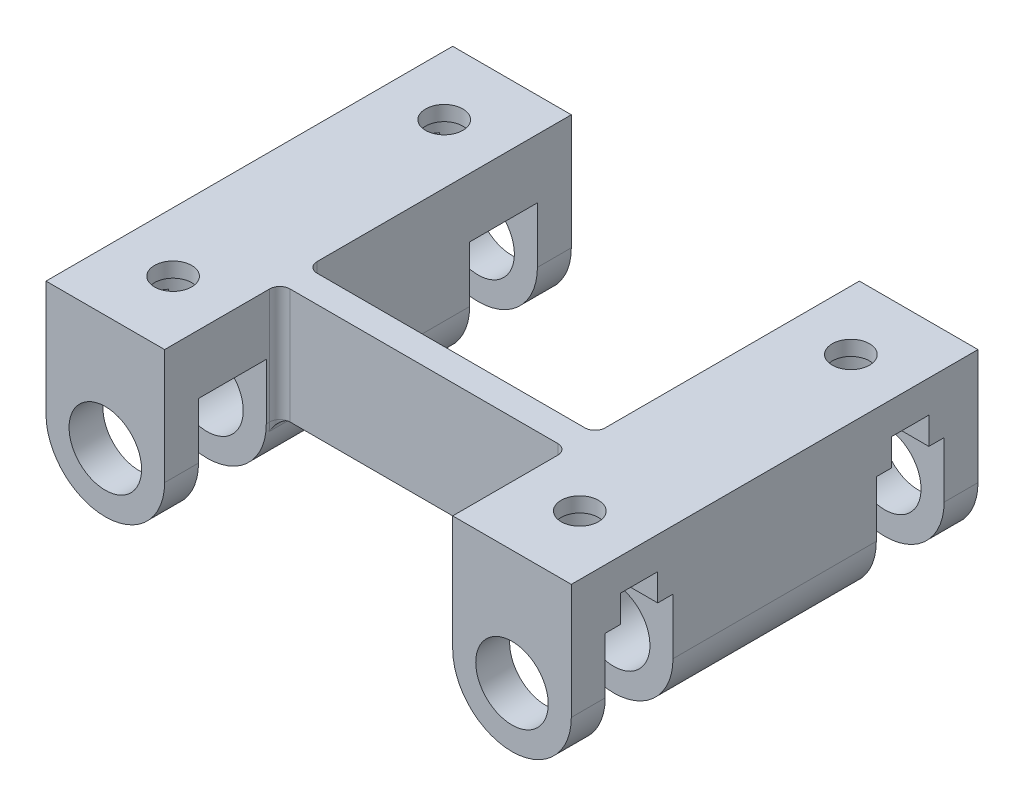
SolidWorks part; units mm, degrees
ref_plane "Front Plane" through (0, 0, 0) normal (0, 0, 1) x (1, 0, 0)
ref_plane "Top Plane" through (0, 0, 0) normal (0, 1, 0) x (1, 0, 0)
ref_plane "Right Plane" through (0, 0, 0) normal (1, 0, 0) x (0, 0, -1)
sketch "Sketch1" plane through (0, 0, 0) normal (0, 0, 1) x (1, 0, 0)
  line L1 (-8.75, 0) -> (8.75, 0)
  line L2 (-8.75, 0) -> (-8.75, 17)
  line L3 (-8.75, 17) -> (8.75, 17)
  line L4 (8.75, 0) -> (8.75, 17)
  circle A0 centre (0, 0) radius 5.35
  circle A1 centre (0, 0) radius 8.75
  dimension "D1" = 10.7
  dimension "D2" = 17.5
  dimension "D3" = 17
  dimension "D4" = 17.5
extrude "Boss-Extrude2" add sketch "Sketch1" along normal mid plane 60 contours L1 A1 A0 | L1 A1 A0 | A1 L4 L3 L2 region at (0, 5.5457, 0) region at (7.05, -0.1957, 0) region at (0, 11.7478, 0)
sketch "Sketch5" plane through (-8.75, 0, 0) normal (-1, 0, 0) x (0, 0, 1)
  line L0 (-30, -8.75) -> (30, -8.75) construction
  line L1 (-25, 8.25) -> (-15, 8.25)
  line L2 (-25, 8.25) -> (-25, -8.75)
  line L3 (-25, -8.75) -> (-15, -8.75)
  line L4 (-15, 8.25) -> (-15, -8.75)
  line L5 (-30, 0) -> (-30, 17) construction
  line L6 (30, 0) -> (30, 17) construction
  line L7 (15, 8.25) -> (25, 8.25)
  line L8 (15, 8.25) -> (15, -8.75)
  line L9 (15, -8.75) -> (25, -8.75)
  line L10 (25, 8.25) -> (25, -8.75)
  dimension "D1" = 5
  dimension "D2" = 10
  dimension "D3" = 17
  dimension "D4" = 5
  dimension "D5" = 10
  dimension "D6" = 17
extrude "Cut-Extrude5" cut sketch "Sketch5" against normal blind 18 contours L2 L1 L4 L3 | L8 L7 L10 L9
sketch "Sketch7" plane through (0, 8.25, 0) normal (0, -1, 0) x (1, 0, 0)
  line L0 (8.75, 15) -> (8.75, 25) construction
  circle A0 centre (0, 20) radius 4.4
  point P7 (8.75, 20)
  dimension "D1" = 8.8
extrude "Cut-Extrude7" cut sketch "Sketch7" against normal blind 6.55
sketch "Sketch8" plane through (0, 14.8, 0) normal (0, -1, 0) x (1, 0, 0)
  line L0 (8.75, 15) -> (8.75, 25) construction
  circle A0 centre (0, 20) radius 2.75
  point P6 (8.75, 20)
  dimension "D1" = 5.5
extrude "Cut-Extrude8" cut sketch "Sketch8" against normal blind 2.2 contours A0
sketch "Sketch9" plane through (0, 8.25, 0) normal (0, -1, 0) x (1, 0, 0)
  line L0 (-8.75, 15) -> (-8.75, 25) construction
  line L1 (0, 17.25) -> (-8.75, 17.25)
  line L2 (0, 17.25) -> (0, 22.75)
  line L3 (0, 22.75) -> (-8.75, 22.75)
  line L4 (-8.75, 17.25) -> (-8.75, 22.75)
  circle A0 centre (0, 20) radius 2.75 construction
  dimension "D1" = 5.5
  dimension "D2" = 8.75
extrude "Cut-Extrude11" cut sketch "Sketch9" against normal blind 4 contours L2 L1 L4 L3
sketch "Sketch10" plane through (0, 8.25, 0) normal (0, -1, 0) x (1, 0, 0)
  line L0 (8.75, -25) -> (8.75, -15) construction
  circle A0 centre (0, -20) radius 4.4
  point P8 (8.75, -20)
extrude "Cut-Extrude12" cut sketch "Sketch10" against normal blind 6.55 contours A0
sketch "Sketch11" plane through (0, 14.8, 0) normal (0, -1, 0) x (-1, 0, 0)
  circle A0 centre (0, 20) radius 2.75
  dimension "D1" = 5.5
extrude "Cut-Extrude13" cut sketch "Sketch11" against normal blind 2.2 contours A0
sketch "Sketch13" plane through (0, 14.8, 0) normal (0, -1, 0) x (1, 0, 0)
  line L0 (-8.75, -25) -> (-8.75, -15) construction
  line L1 (0, -22.75) -> (-8.75, -22.75)
  line L2 (0, -22.75) -> (0, -17.25)
  line L3 (0, -17.25) -> (-8.75, -17.25)
  line L4 (-8.75, -22.75) -> (-8.75, -17.25)
  circle A0 centre (0, -20) radius 2.75 construction
  dimension "D1" = 5.5
  dimension "D2" = 8.75
extrude "Cut-Extrude14" cut sketch "Sketch13" against normal blind 4 from offset 6.55 contours L2 L1 L4 L3
ref_plane "Plane1" through (30, 0, 0) normal (1, 0, 0) x (0, 0, -1)
sketch "Sketch14" plane through (8.75, 0, 0) normal (1, 0, 0) x (0, 0, -1)
  line L0 (-30, 17) -> (30, 17) construction
  line L1 (-13, 17) -> (-9, 17)
  line L2 (-13, 17) -> (-13, 0)
  line L3 (-13, 0) -> (-9, 0)
  line L4 (-9, 17) -> (-9, 0)
  line L5 (-15, 0) -> (15, 0) construction
  line L6 (-30, 0) -> (-30, 17) construction
  dimension "D1" = 4
  dimension "D2" = 17
extrude "Boss-Extrude4" add sketch "Sketch14" along normal up to surface (21.25 mm away) up to plane "Plane1"
mirror "Mirror4" about plane through (30, 0, 0) normal (1, 0, 0) of "Boss-Extrude4"
mirror "Mirror5" about plane through (30, 0, 0) normal (1, 0, 0) of "Boss-Extrude2"
mirror "Mirror6" about plane through (30, 0, 0) normal (1, 0, 0) of "Cut-Extrude14", "Cut-Extrude13", "Cut-Extrude12", "Cut-Extrude11", "Cut-Extrude8", "Cut-Extrude7", "Cut-Extrude5"
fillet "Fillet1" radius 1.5 2 edges at (51.25, 0, 11) (8.75, 0, 11)
fillet "Fillet2" radius 1.5 8 edges at (8.7264, -0.642, 13) (51.2736, -0.642, 13) (51.2736, -0.642, 9) (8.7264, -0.642, 9) (8.75, 8.5, 9) (51.25, 8.5, 9) (8.75, 8.5, 13) (51.25, 8.5, 13)
